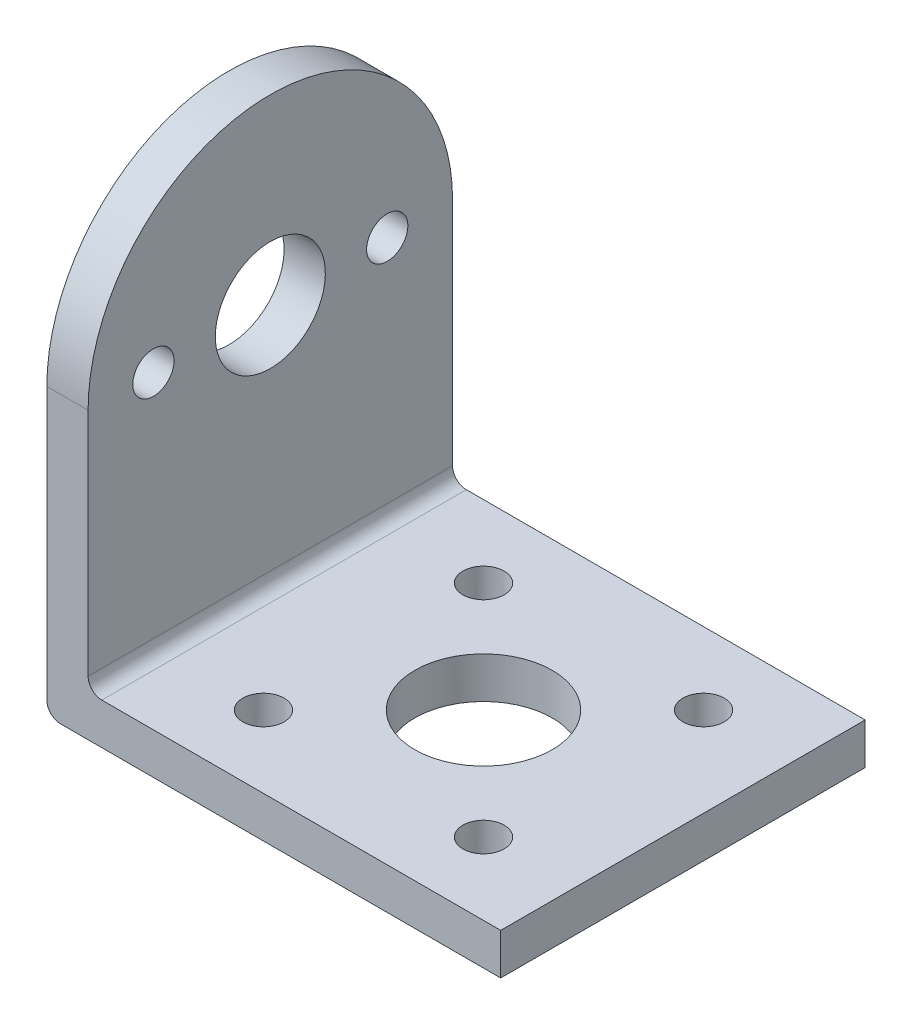
SolidWorks part; units mm, degrees
ref_plane "前视基准面" through (0, 0, 0) normal (0, 0, 1) x (1, 0, 0)
ref_plane "上视基准面" through (0, 0, 0) normal (0, 1, 0) x (1, 0, 0)
ref_plane "右视基准面" through (0, 0, 0) normal (1, 0, 0) x (0, 0, -1)
other "Configuration Table"
sketch "草图2" plane through (0, 0, 0) normal (0, 0, 1) x (1, 0, 0)
  line L0 (0, 1) -> (0, 34)
  line L1 (0, 34) -> (3, 34)
  line L2 (3, 34) -> (3, 4)
  line L3 (4, 3) -> (33, 3)
  line L4 (33, 3) -> (33, 0)
  line L5 (33, 0) -> (1, 0)
  arc A0 (0, 1) -> (1, 0) centre (1, 1) ccw
  arc A1 (3, 4) -> (4, 3) centre (4, 4) ccw
  point P13 (0, 0)
  dimension "D5" = 1
  dimension "D6" = 1
  dimension "D1" = 3
  dimension "D2" = 34
  dimension "D3" = 33
  dimension "D4" = 3
extrude "凸台-拉伸1" add sketch "草图2" along normal blind 26.5
sketch "草图3" plane through (3, 0, 0) normal (1, 0, 0) x (0, 0, -1)
  line L0 (-26.5, 4) -> (-26.5, 34) construction
  line L1 (0, 4) -> (0, 34) construction
  line L2 (-26.5, 20.75) -> (0, 20.75)
  line L3 (-13.25, 37.4884) -> (-13.25, -1.2841) construction
  line L6 (0, 4) -> (0, 34)
  line L7 (0, 34) -> (-26.5, 34)
  line L8 (-26.5, 34) -> (-26.5, 4)
  line L9 (-26.5, 4) -> (0, 4)
  line L10 (0, 4) -> (0, 34)
  line L11 (0, 34) -> (-26.5, 34)
  line L12 (-26.5, 34) -> (-26.5, 4)
  line L13 (-26.5, 4) -> (0, 4)
  arc A0 (-26.5, 20.75) -> (0, 20.75) centre (-13.25, 20.75) cw
  circle A1 centre (-13.25, 20.75) radius 4
  circle A2 centre (-4.75, 20.75) radius 1.5
  circle A3 centre (-21.75, 20.75) radius 1.5
  line M1 (0, 4) -> (0, 34)
  line M2 (0, 34) -> (-26.5, 34)
  line M3 (-26.5, 34) -> (-26.5, 4)
  dimension "D1" = 13.25
  dimension "D3" = 3
  dimension "D4" = 8
  dimension "D5" = 17
  dimension "D2" = 0
extrude "切除-拉伸1" cut sketch "草图3" against normal through all contours A0 M2 M1 | A0 L11 M3 | A2 | A3 region at (3, 31.0404, 2.9596) region at (3, 31.0404, 23.5404)
extrude "切除-拉伸2" cut sketch "草图3<3>" against normal through all contours A1
sketch "草图3<3>" plane through (3, 0, 0) normal (1, 0, 0) x (0, 0, -1) same geometry as "草图3"
sketch "草图4" plane through (0, 3, 0) normal (0, 1, 0) x (1, 0, 0)
  line L0 (35.0554, -13.25) -> (-5.0871, -13.25) construction
  line L1 (18.5, 3.3249) -> (18.5, -30.9689) construction
  line L6 (33, 0) -> (4, 0)
  line L7 (4, 0) -> (4, -26.5)
  line L8 (4, -26.5) -> (33, -26.5)
  line L9 (33, -26.5) -> (33, 0)
  line L10 (33, 0) -> (4, 0)
  line L11 (4, 0) -> (4, -26.5)
  line L12 (4, -26.5) -> (33, -26.5)
  line L13 (33, -26.5) -> (33, 0)
  circle A0 centre (18.5, -13.25) radius 5
  circle A1 centre (26.5, -5.25) radius 1.5
  circle A2 centre (10.5, -5.25) radius 1.5
  circle A3 centre (10.5, -21.25) radius 1.5
  circle A4 centre (26.5, -21.25) radius 1.5
  dimension "D2" = 3
  dimension "D4" = 10
  dimension "D3" = 16
  dimension "D5" = 16
  dimension "D1" = 0
extrude "切除-拉伸3" cut sketch "草图4" against normal through all both and the other way through all contours A3 | A2 | A1 | A0 | A4 region at (18.5, 3, 13.25) region at (26.5, 3, 5.25) region at (10.5, 3, 5.25) region at (10.5, 3, 21.25) region at (26.5, 3, 21.25)
